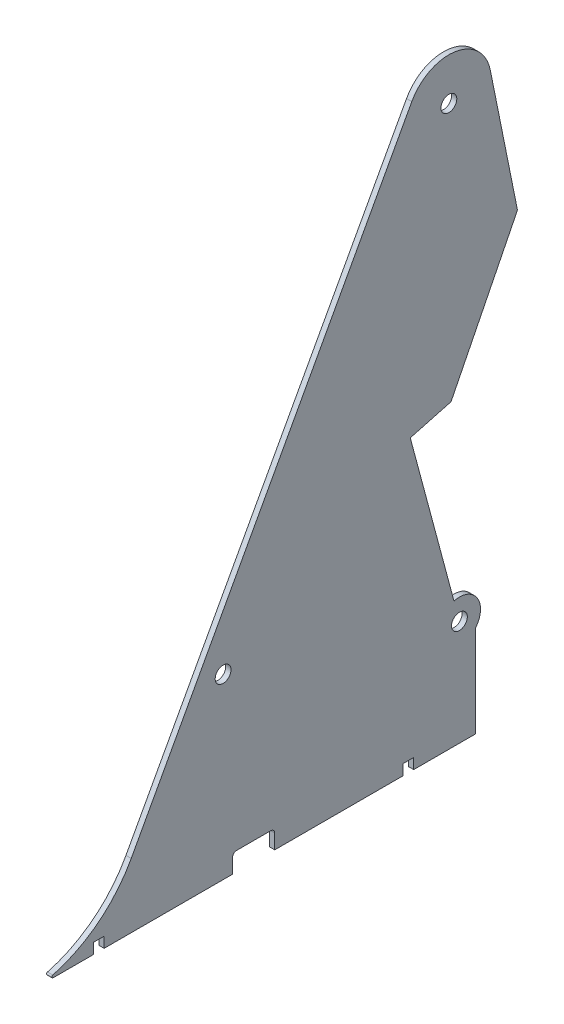
SolidWorks part; units mm, degrees
ref_plane "Front Plane" through (0, 0, 0) normal (0, 0, 1) x (1, 0, 0)
ref_plane "Top Plane" through (0, 0, 0) normal (0, 1, 0) x (1, 0, 0)
ref_plane "Right Plane" through (0, 0, 0) normal (1, 0, 0) x (0, 0, -1)
sketch "Sketch1" plane through (0, 0, 0) normal (1, 0, 0) x (0, 0, -1)
  line L0 (0, 0) -> (0, 55.0997)
  line L6 (-39.108, 173.9053) -> (-14.5735, 180.4793)
  line L7 (-14.5735, 180.4793) -> (25.4, 260.35)
  line L8 (25.4, 260.35) -> (9.0239, 341.5703)
  line L9 (-38.1812, 348.6988) -> (-207.0089, 38.7176)
  line L10 (-254, 0) -> (0, 0)
  line L12 (-254.2054, 1.5605) -> (-207.9989, 13.9415) construction
  line L13 (-39.108, 173.9053) -> (-12.812, 75.7673)
  line L14 (-12.812, 75.7673) -> (13.738, 82.8813) construction
  arc A0 (9.0239, 341.5703) -> (-38.1812, 348.6988) centre (-15.875, 336.55) ccw
  arc A1 (-254, 0) -> (-254.2054, 1.5605) centre (-254, 0.7937) cw
  arc A2 (-254.2054, 1.5605) -> (-207.0089, 38.7176) centre (-273.9274, 75.164) ccw
  arc A3 (0, 55.0997) -> (-12.812, 75.7673) centre (-9.525, 63.5) ccw
  dimension "D2" = 25.4
  dimension "D6" = 0.7937
  dimension "D7" = 76.2
  dimension "D12" = 12.7
  dimension "D1" = 15.875
  dimension "D3" = 336.55
  dimension "D4" = 25.4
  dimension "D5" = 101.6
  dimension "D8" = 254
  dimension "D9" = 15
  dimension "D10" = 9.525
  dimension "D11" = 63.5
  dimension "D13" = 76.2
  dimension "D14" = 25.4
  dimension "D15" = 15
extrude "Boss-Extrude1" add sketch "Sketch1" along normal blind 3.175
sketch "Sketch2" plane through (3.175, 0, 0) normal (1, 0, 0) x (0, 0, -1)
  line L16 (-146.05, 8.7909) -> (-146.05, -0.3034) construction
  line L17 (-123.0376, 11.1785) -> (-143.6624, 11.1785) construction
  line L18 (-120.65, -0.3034) -> (-120.65, 8.7909) construction
  line L19 (-146.05, 8.7909) -> (-146.05, 0)
  line L20 (-123.0376, 11.1785) -> (-143.6624, 11.1785)
  line L21 (-120.65, 0) -> (-120.65, 8.7909)
  line L23 (-37.0504, 0) -> (-37.0504, 6.35) construction
  line L24 (-43.4004, 0) -> (-37.0504, 0) construction
  line L25 (-146.05, 0) -> (-120.65, 0)
  line L26 (-254, 0) -> (0, 0) construction
  line L27 (-43.4004, 6.35) -> (-43.4004, 0) construction
  line L28 (-37.0504, 6.35) -> (-43.4004, 6.35) construction
  line L29 (-37.0504, 0) -> (-37.0504, 6.35)
  line L30 (-43.4004, 0) -> (-37.0504, 0)
  line L31 (-43.4004, 6.35) -> (-43.4004, 0)
  line L32 (-37.0504, 6.35) -> (-43.4004, 6.35)
  line L33 (-223.2996, 0) -> (-223.2996, 6.35) construction
  line L34 (-229.6496, 0) -> (-223.2996, 0) construction
  line L35 (-229.6496, 6.35) -> (-229.6496, 0) construction
  line L36 (-223.2996, 6.35) -> (-229.6496, 6.35) construction
  line L37 (-223.2996, 0) -> (-223.2996, 6.35)
  line L38 (-229.6496, 0) -> (-223.2996, 0)
  line L39 (-229.6496, 6.35) -> (-229.6496, 0)
  line L40 (-223.2996, 6.35) -> (-229.6496, 6.35)
  arc A0 (-143.6624, 11.1785) -> (-146.05, 8.7909) centre (-143.6624, 8.7909) ccw construction
  arc A1 (-120.65, 8.7909) -> (-123.0376, 11.1785) centre (-123.0376, 8.7909) ccw construction
  arc A2 (-143.6624, 11.1785) -> (-146.05, 8.7909) centre (-143.6624, 8.7909) ccw
  arc A3 (-120.65, 8.7909) -> (-123.0376, 11.1785) centre (-123.0376, 8.7909) ccw
extrude "Cut-Extrude1" cut sketch "Sketch2" against normal through all
sketch "Sketch3" plane through (3.175, 0, 0) normal (1, 0, 0) x (0, 0, -1)
  point P0 (-15.875, 336.55)
  point P4 (-9.525, 63.5)
hole_wizard "3/8 Clearance Hole1" positions "Sketch3" profile "Sketch4" hole size "3/8" standard "ANSI Inch" end condition up to next
sketch "Sketch4" plane through (3.175, 336.55, 15.875) normal (0, 1, 0) x (0, 0, -1)
  line L0 (0, 0) -> (0, 3.175)
  line L1 (0, 3.175) -> (4.7625, 3.175)
  line L2 (4.7625, 3.175) -> (4.7625, 0)
  line L5 (4.7625, 0) -> (0, 0)
  line L11 (0, -6.35) -> (0, 107.95) construction
  dimension "Thru Hole Dia." = 9.525
  dimension "Thru Hole Depth" = 3.175
sketch "Sketch5" plane through (3.175, 0, 0) normal (1, 0, 0) x (0, 0, -1)
  line L0 (-9.525, 63.5) -> (26.6637, 27.8487)
  line L1 (26.6637, 27.8487) -> (26.7576, 15.3058)
  line L2 (22.1401, 32.3051) -> (-24.5595, 22.9623)
  line L3 (-15.875, 19.05) -> (-24.5595, 22.9623)
  line L4 (0, 0) -> (0, 55.0997) construction
  line L5 (-15.875, 19.05) -> (-33.6895, 12.3011)
  line L6 (-33.6895, 12.3011) -> (-54.7505, 169.5016)
  line L7 (50.8, 0) -> (50.8, 73.5762) construction
  dimension "D1" = 44.45
  dimension "D2" = 50.8
  dimension "D3" = 45
  dimension "D4" = 60.325
  dimension "D5" = 19.05
  dimension "D6" = 15.875
  dimension "D7" = 9.525
  dimension "D8" = 47.625
  dimension "D9" = 19.05
  dimension "D10" = 45
  dimension "D11" = 50.8
sketch "Sketch6" plane through (3.175, 0, 0) normal (1, 0, 0) x (0, 0, -1)
  line L1 (-151.7209, 107.0402) -> (-165.6623, 114.6332) construction
  line L3 (-38.1812, 348.6988) -> (-207.0089, 38.7176) construction
  circle A2 centre (-151.7209, 107.0402) radius 4.7625
  dimension "D4" = 9.525
  dimension "D5" = 15.875
  dimension "D6" = 266.7
extrude "Cut-Extrude2" cut sketch "Sketch6" against normal through all
sketch "Sketch8" [suppressed] plane through (3.175, 0, 0) normal (1, 0, 0) x (0, 0, -1)
  circle A0 centre (-149.0973, 86.4574) radius 4.7625
  circle A1 centre (-163.9937, 72.1143) radius 2.032
  circle A2 centre (-110.1457, 101.5783) radius 2.032
  circle A3 centre (-163.9937, 72.1143) radius 1.905 construction
  circle A4 centre (-110.1457, 101.5783) radius 1.985 construction
  dimension "D1" = 25.4
  dimension "D2" = 9.525
  dimension "D3" = 4.064
extrude "Cut-Extrude3" [suppressed] cut sketch "Sketch8" against normal through all both and the other way through all
sketch "Sketch9" [suppressed] plane through (3.175, 0, 0) normal (1, 0, 0) x (0, 0, -1)
  circle A8 centre (-163.9937, 72.1143) radius 4.445
  circle A9 centre (-163.9937, 72.1143) radius 4.445
  dimension "D1" = 2.54
